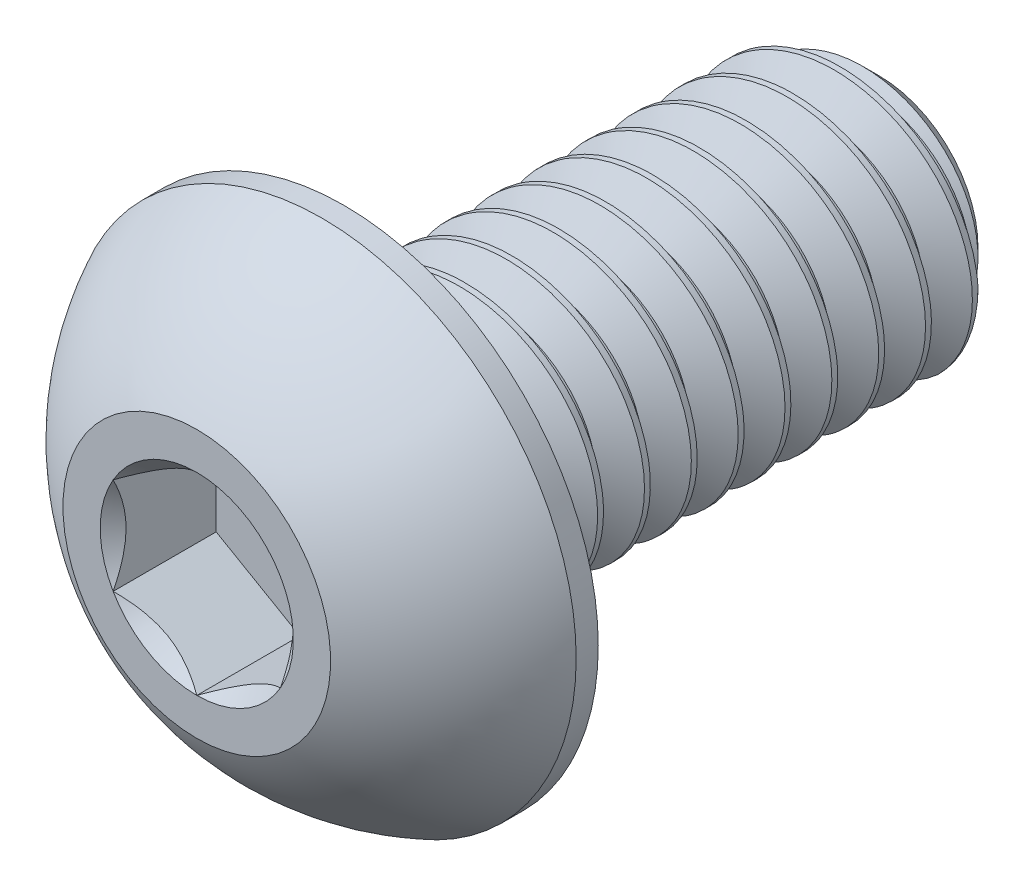
SolidWorks part; units mm, degrees
ref_plane "Front" through (0, 0, 0) normal (0, 0, 1) x (1, 0, 0)
ref_plane "Top" through (0, 0, 0) normal (0, 1, 0) x (1, 0, 0)
ref_plane "Right" through (0, 0, 0) normal (1, 0, 0) x (0, 0, -1)
sketch "Sketch1" plane through (0, 0, 0) normal (1, 0, 0) x (0, 0, -1)
  line L2 (2.2, 2) -> (10.2, 2)
  line L3 (10.2, 2) -> (10.2, 0)
  line L4 (10.2, 0) -> (2.2, 0)
  line L6 (1.87, 3.8) -> (2.2, 3.8) construction
  line L7 (10.2, 2) -> (10.2, -2) construction
  line L8 (0, 0) -> (2.2, 0) construction
  line L9 (2.2, 3.8) -> (2.2, -3.8) construction
  line L11 (2.2, 2) -> (2.2, 0)
  line L13 (0, 1.25) -> (0, -1.25) construction
  line L14 (0, 1.25) -> (0, 2) construction
  arc A3 (0, 2) -> (1.87, 3.8) centre (3.7264, 0) cw construction
  dimension "D1" = 0.33
revolve "Revolve1" add sketch "Sketch1" angle 360 mid plane about L4
sketch "Sketch3" plane through (0, 0, -10.2) normal (0, 0, -1) x (-1, 0, 0)
  circle A0 centre (0, 0) radius 2
curve "Helix/Spiral1" pitch 0.7 height 8.7 radius 2 centre (0, 0, -10.2) axis (0, 0, 1) start towards (0, 1, 0)
sketch "Sketch2" plane through (0, 0, 0) normal (1, 0, 0) x (0, 0, -1)
  line L0 (10.2, 2) -> (10.8125, 2)
  line L1 (10.8125, 2) -> (10.55, 1.5453)
  line L2 (10.55, 1.5453) -> (10.4625, 1.5453)
  line L3 (10.4625, 1.5453) -> (10.2, 2)
  line L4 (10.3313, 1.7727) -> (10.6813, 1.7727) construction
  dimension "D1" = 60
  dimension "D2" = 0.0875
  dimension "D3" = 0.35
chamfer "Chamfer1" distance 0.525 angle 45 1 edges at (0, 2, -10.2)
sweep "Cut-Sweep1" cut profiles "Sketch2" path "Helix/Spiral1" align with end faces yes
sketch "Sketch7" plane through (0, 0, 0) normal (1, 0, 0) x (0, 0, -1)
  line L6 (1.87, 3.8) -> (2.2, 3.8) construction
  line L8 (0, 0) -> (2.2, 0) construction
  line L11 (2.2, 3.8) -> (2.2, -3.8) construction
  line L12 (1.87, 3.8) -> (2.2, 3.8)
  line L13 (0, 0) -> (2.2, 0)
  line L14 (0, 1.25) -> (0, -1.25) construction
  line L15 (2.2, 3.8) -> (2.2, 0)
  line L16 (0, 2) -> (0, 0)
  arc A2 (1.87, 3.8) -> (0, 2) centre (3.7264, 0) ccw construction
  arc A3 (1.87, 3.8) -> (0, 2) centre (3.7264, 0) ccw
revolve "Revolve2" add sketch "Sketch7" angle 360 mid plane about L13
sketch "Sketch5" plane through (0, 0, 0) normal (0, 0, 1) x (1, 0, 0)
  line L1 (1.25, -0.7217) -> (1.25, 0.7217)
  line L2 (1.25, 0.7217) -> (0, 1.4434)
  line L3 (0, 1.4434) -> (-1.25, 0.7217)
  line L4 (-1.25, 0.7217) -> (-1.25, -0.7217)
  line L5 (-1.25, -0.7217) -> (0, -1.4434)
  line L6 (0, -1.4434) -> (1.25, -0.7217)
  circle A0 centre (0, 0) radius 1.25 construction
extrude "Cut-Extrude2" cut sketch "Sketch5" against normal blind 1.54
sketch "Sketch6" plane through (0, 0, 0) normal (0, 0, 1) x (1, 0, 0)
  circle A0 centre (0, 0) radius 1.4434
extrude "Cut-Extrude3" cut sketch "Sketch6" against normal blind 1.54 draft 45
sketch "Sketch9" plane through (0, 0, -2.2) normal (0, 0, 1) x (1, 0, 0)
  circle A2 centre (0, 0) radius 2
extrude "Boss-Extrude2" [suppressed] add sketch "Sketch9" against normal offset from surface (5 mm away) 28.575 up to face at (0, 1.475, -10.2)
sketch "Sketch10" plane through (0, 0, 0) normal (1, 0, 0) x (0, 0, -1)
  line L0 (10.2, 2) -> (10.2, -2) construction
  point P0 (9.15, -2)
  dimension "D1" = 1.05
equation "\"D3@Helix/Spiral1\" = \"Lg@Sketch1\" + \"D4@Helix/Spiral1\""
equation "\"D2@Sketch2\" = \"D4@Helix/Spiral1\" * .125"
equation "\"D3@Sketch2\" = \"D4@Helix/Spiral1\" * .5"
equation "\"D1@Chamfer1\" = \"D4@Helix/Spiral1\" * .75"
equation "\"D1@Cut-Extrude2\" = \"Head Ht@Sketch1\" * .7"
equation "\"D1@Sketch1\" = \"Head Ht@Sketch1\" * .15"
equation "\"D1@Sketch10\" = \"D4@Helix/Spiral1\" * 1.5"
equation "\"D1@Cut-Extrude3\" = \"D1@Cut-Extrude2\""
